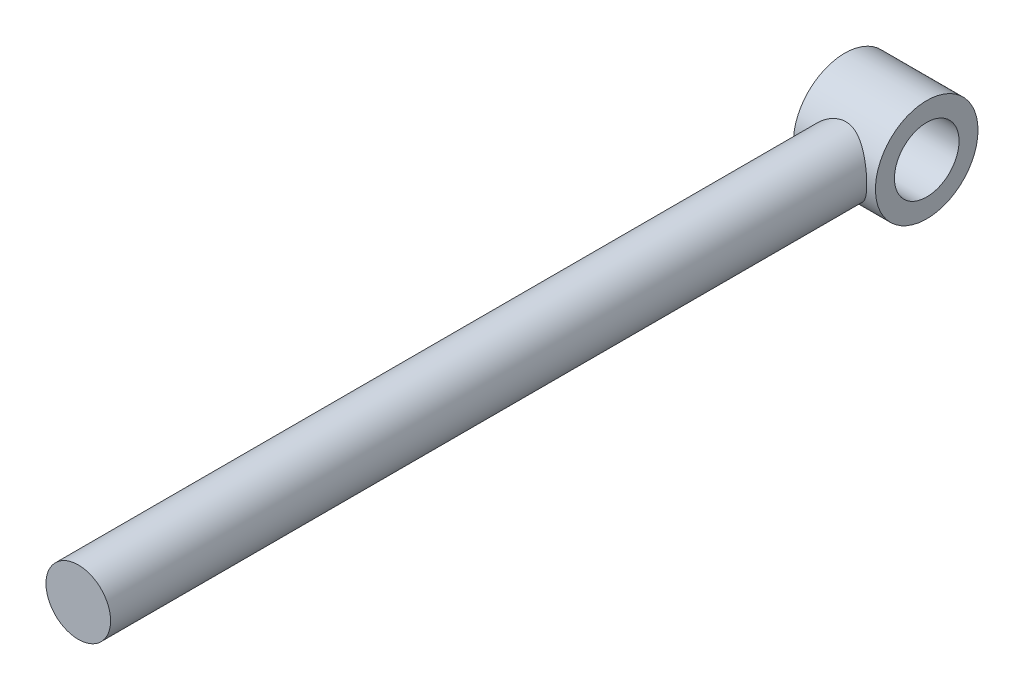
SolidWorks part; units mm, degrees
ref_plane "Front Plane" through (0, 0, 0) normal (1, 0, 0) x (0, 1, 0)
ref_plane "Top Plane" through (0, 0, 0) normal (0, 0, 1) x (0, 1, 0)
ref_plane "Right Plane" through (0, 0, 0) normal (0, 1, 0) x (-1, 0, 0)
sketch "Sketch1" plane through (0, 0, 0) normal (1, 0, 0) x (0, 1, 0)
  circle A0 centre (0, 0) radius 4
  circle A1 centre (0, 0) radius 6.35
  dimension "D1" = 8
  dimension "D2" = 12.7
sketch "Sketch2" plane through (0, 0, 0) normal (0, 0, 1) x (0, 1, 0)
  circle A0 centre (0, 0) radius 4
extrude "Boss-Extrude1" add sketch "Sketch2" along normal blind 100
extrude "Boss-Extrude2" add sketch "Sketch1" along normal mid plane 10.16 contours A1
extrude "Cut-Extrude1" cut sketch "Sketch1<3>" against normal mid plane 10.16 contours A0
sketch "Sketch1<3>" plane through (0, 0, 0) normal (1, 0, 0) x (0, 1, 0) same geometry as "Sketch1"
